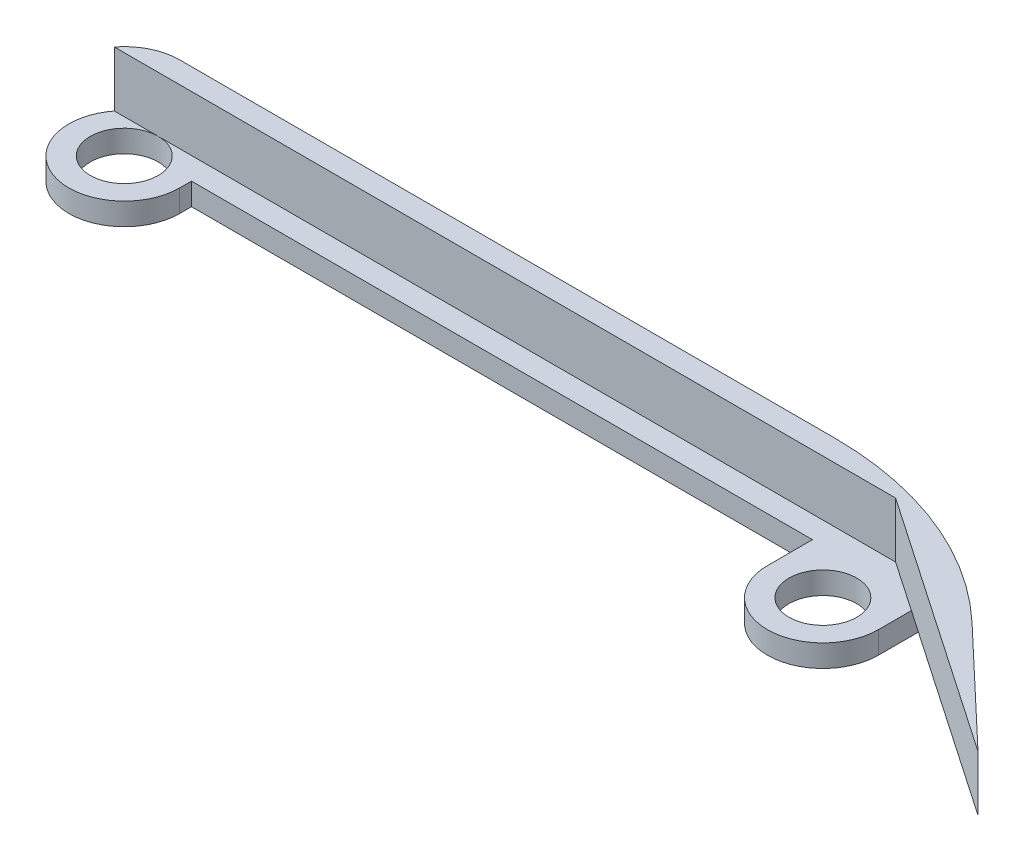
SolidWorks part; units mm, degrees
ref_plane "Front Plane" through (0, 0, 0) normal (0, 0, 1) x (1, 0, 0)
ref_plane "Top Plane" through (0, 0, 0) normal (0, 1, 0) x (1, 0, 0)
ref_plane "Right Plane" through (0, 0, 0) normal (1, 0, 0) x (0, 0, -1)
sketch "Sketch1" plane through (0, 0, 0) normal (0, 1, 0) x (1, 0, 0)
  line L2 (-5, 0) -> (-5, 5)
  line L5 (-5, 5) -> (71, 5)
  line L9 (71, -3) -> (71, 5)
  line L13 (5, 3.06) -> (61, 3.06)
  line L18 (61, -3) -> (61, 3.06)
  line L19 (5, 0) -> (5, 3.06)
  circle A6 centre (0, 0) radius 3.06
  arc A7 (-5, 0) -> (5, 0) centre (0, 0) ccw
  circle A8 centre (66, -3) radius 3.06
  arc A11 (61, -3) -> (71, -3) centre (66, -3) ccw
  dimension "D5" = 3
  dimension "D6" = 10
  dimension "D2" = 10
  dimension "D1" = 6.12
  dimension "D3" = 6.12
  dimension "D4" = 66
extrude "Boss-Extrude1" add sketch "Sketch1" along normal blind 2
sketch "Sketch4" plane through (0, 0, 0) normal (0, -1, 0) x (-1, 0, 0)
  line L0 (5, 5) -> (-71, 5)
  line L2 (-71, 5) -> (-90, -13.0108)
  line L4 (-90, -13.0108) -> (-66.5, 3.06)
  line L8 (-66.5, 3.06) -> (5, 3.06)
  line L9 (5, 5) -> (5, 0) construction
  line L10 (5, 3.06) -> (5, 5)
  dimension "D1" = 4.5
extrude "Boss-Extrude2" add sketch "Sketch4" against normal blind 5 from offset 2 offset against normal yes
sketch "Sketch6" plane through (0, 0, 0) normal (0, -1, 0) x (-1, 0, 0)
  line L0 (-61, 3.06) -> (-61, -3) construction
  line L1 (-5, 3.06) -> (-61, 3.06)
  line L2 (-5, 3.06) -> (-5, 1.06)
  line L3 (-5, 1.06) -> (-61, 1.06)
  line L4 (-61, 3.06) -> (-61, 1.06)
  dimension "D1" = 2
extrude "Boss-Extrude3" add sketch "Sketch6" against normal up to surface (2 mm away) up to face at (0, 2, -0.1867)
fillet "Fillet1" radius 30 2 edges at (71, 1, -5) (71, 4.5, -5)
fillet "Fillet2" radius 5 5 edges at (-5, 3.5, -5) (-5, 2, -1.53) (-5, 7, -4.03) (-5, 4.5, -3.06) (-5, 0, -2.5)
